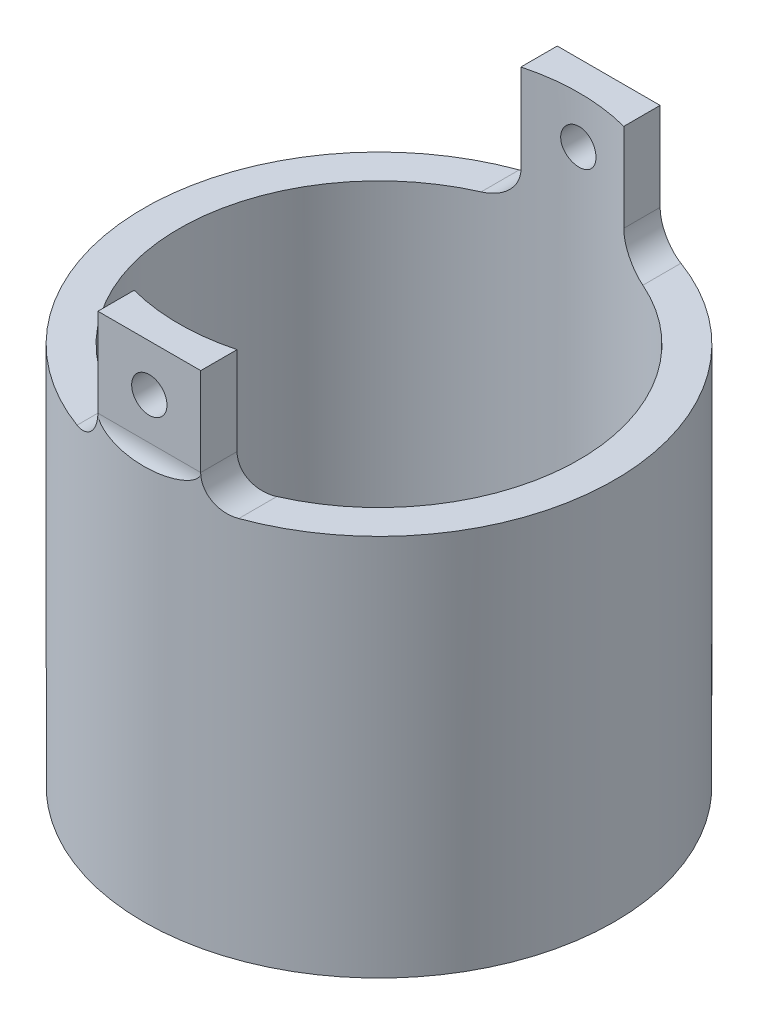
SolidWorks part; units mm, degrees
ref_plane "Спереди" through (0, 0, 0) normal (0, 0, 1) x (1, 0, 0)
ref_plane "Сверху" through (0, 0, 0) normal (0, 1, 0) x (1, 0, 0)
ref_plane "Справа" through (0, 0, 0) normal (1, 0, 0) x (0, 0, -1)
sketch "Sketch1" plane through (0, 0, 0) normal (0, 1, 0) x (1, 0, 0)
  circle A0 centre (0, 0) radius 40
extrude "Boss-Extrude1" add sketch "Sketch1" along normal blind 5
sketch "Sketch2" plane through (0, 5, 0) normal (0, 1, 0) x (1, 0, 0)
  circle A0 centre (0, 0) radius 40
  circle A1 centre (0, 0) radius 34
  circle A2 centre (0, 0) radius 40 construction
  dimension "D1" = 6
extrude "Boss-Extrude2" add sketch "Sketch2" along normal blind 60
sketch "Sketch3" plane through (0, 65, 0) normal (0, 1, 0) x (1, 0, 0)
  line L0 (0, 0) -> (15.1664, 0)
  line L5 (-8.7384, 39.0276) -> (8.7384, 39.0276)
  line L6 (-8.7384, 39.0276) -> (-8.7384, 31.994)
  line L7 (-8.7384, 31.994) -> (8.7384, 31.994)
  line L8 (8.7384, 39.0276) -> (8.7384, 31.994)
  line L9 (-8.7384, 39.0276) -> (8.7384, 31.994) construction
  line L10 (-8.7384, 31.994) -> (8.7384, 39.0276) construction
  line L11 (-8.7384, -31.994) -> (8.7384, -31.994)
  line L12 (8.7384, -39.0276) -> (8.7384, -31.994)
  line L13 (-8.7384, -39.0276) -> (8.7384, -39.0276)
  line L14 (-8.7384, -39.0276) -> (-8.7384, -31.994)
  point P0 (0, 35.5108)
  point P1 (0, 0)
  point P14 (0, 0)
  point P15 (0, 0)
  circle M6 centre (0, 0) radius 34
extrude "Boss-Extrude3" add sketch "Sketch3" along normal blind 20 contours L14 L13 L12 M6 | L8 L5 L6 M6 region at (0, 65, -36.3141) region at (0, 65, 36.3141)
fillet "Fillet1" radius 5 4 edges at (8.7384, 65, 35.9427) (-8.7384, 65, 35.9427) (8.7384, 65, -35.9427) (-8.7384, 65, -35.9427)
sketch "Sketch4" plane through (0, 0, -39.0276) normal (0, 0, -1) x (-1, 0, 0)
  circle A0 centre (0, 77.048) radius 3
  point P2 (0, 79.2893)
  point P3 (0, 77.048)
extrude "Cut-Extrude1" cut sketch "Sketch4" against normal blind 95
fillet "Fillet2" radius 5 1 edges at (0, 5, 34)
sketch "Sketch5" plane through (0, 5, 0) normal (0, 1, 0) x (1, 0, 0)
  circle A0 centre (0, 0) radius 23.5
extrude "Boss-Extrude4" [suppressed] add sketch "Sketch5" along normal blind 95
fillet "Fillet3" radius 5 2 edges at (0, 65, 39.0276) (0, 65, -39.0276)
